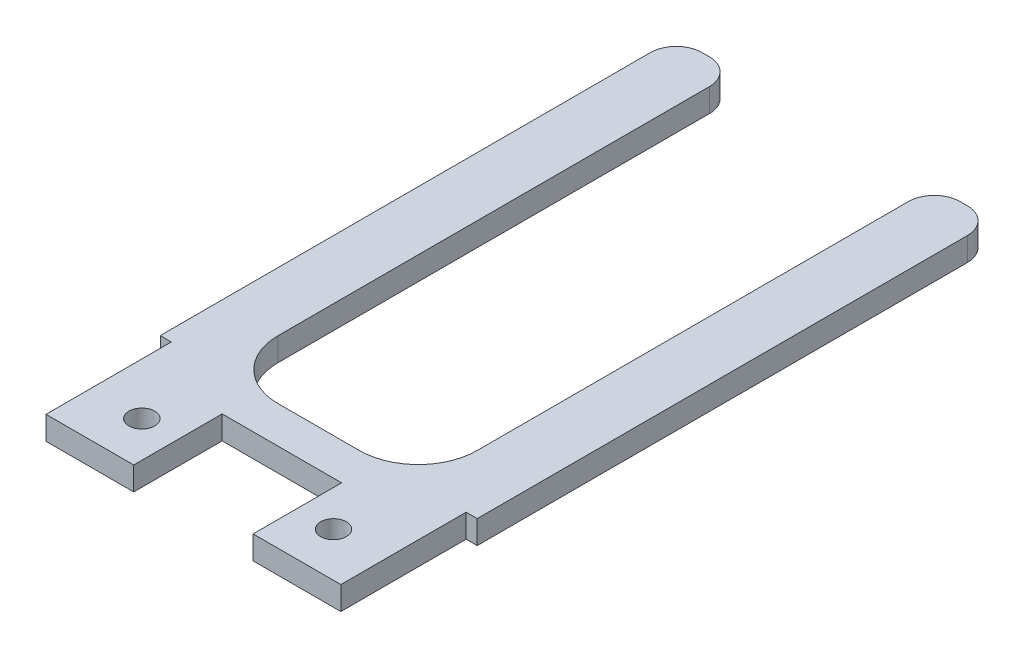
SolidWorks part; units mm, degrees
ref_plane "Alzado" through (0, 0, 0) normal (0, 0, 1) x (1, 0, 0)
ref_plane "Planta" through (0, 0, 0) normal (0, 1, 0) x (1, 0, 0)
ref_plane "Vista lateral" through (0, 0, 0) normal (1, 0, 0) x (0, 0, -1)
sketch "Croquis1" plane through (0, 0, 0) normal (0, 1, 0) x (1, 0, 0)
  line L0 (8.1, 0) -> (-8.1, 0)
  line L1 (-8.1, 0) -> (-8.1, -12)
  line L2 (-8.1, -12) -> (-20, -12)
  line L3 (-20, -12) -> (-20, 5)
  line L4 (-20, 5) -> (-21.5, 5)
  line L5 (-21.5, 5) -> (-21.5, 71.5)
  line L6 (-18, 75) -> (-17, 75)
  line L7 (-13.5, 71.5) -> (-13.5, 5)
  line L8 (-13.5, 5) -> (13.5, 5)
  line L9 (0, 5) -> (0, 0)
  line L10 (0, 20.5) -> (0, -26.8333) construction
  line L11 (-20, -6) -> (-8.1, -6) construction
  line L12 (13.5, 71.5) -> (13.5, 5)
  line L13 (18, 75) -> (17, 75)
  line L14 (21.5, 5) -> (21.5, 71.5)
  line L15 (20, 5) -> (21.5, 5)
  line L16 (20, -12) -> (20, 5)
  line L17 (8.1, -12) -> (20, -12)
  line L18 (8.1, 0) -> (8.1, -12)
  circle A0 centre (-13, -6) radius 1.75
  circle A1 centre (13, -6) radius 1.75
  arc A2 (13.5, 71.5) -> (17, 75) centre (17, 71.5) cw
  arc A3 (-17, 75) -> (-13.5, 71.5) centre (-17, 71.5) cw
  arc A4 (18, 75) -> (21.5, 71.5) centre (18, 71.5) cw
  arc A5 (-21.5, 71.5) -> (-18, 75) centre (-18, 71.5) cw
  point P29 (13.5, 75)
  point P32 (-13.5, 75)
  point P35 (21.5, 75)
  point P38 (-21.5, 75)
  point P39 (-8.1, -6)
  dimension "D8" = 3.5
  dimension "D9" = 3.5
  dimension "D1" = 8
  dimension "D2" = 11.9
  dimension "D3" = 20
  dimension "D4" = 21.5
  dimension "D5" = 5
  dimension "D6" = 17
  dimension "D7" = 70
  dimension "D10" = 4.9
extrude "Saliente-Extruir1" add sketch "Croquis1" along normal mid plane 3.175 contours L0 L18 L17 L16 L15 L14 L13 L12 L8 L9 A1 | L9 L8 L7 L6 L5 L4 L3 L2 L1 L0 A0 region at (15.9778, 0, -27.2371) region at (-15.9778, 0, -27.2371)
fillet "Redondeo1" radius 8 2 edges at (13.5, 0, -5) (-13.5, 0, -5)
